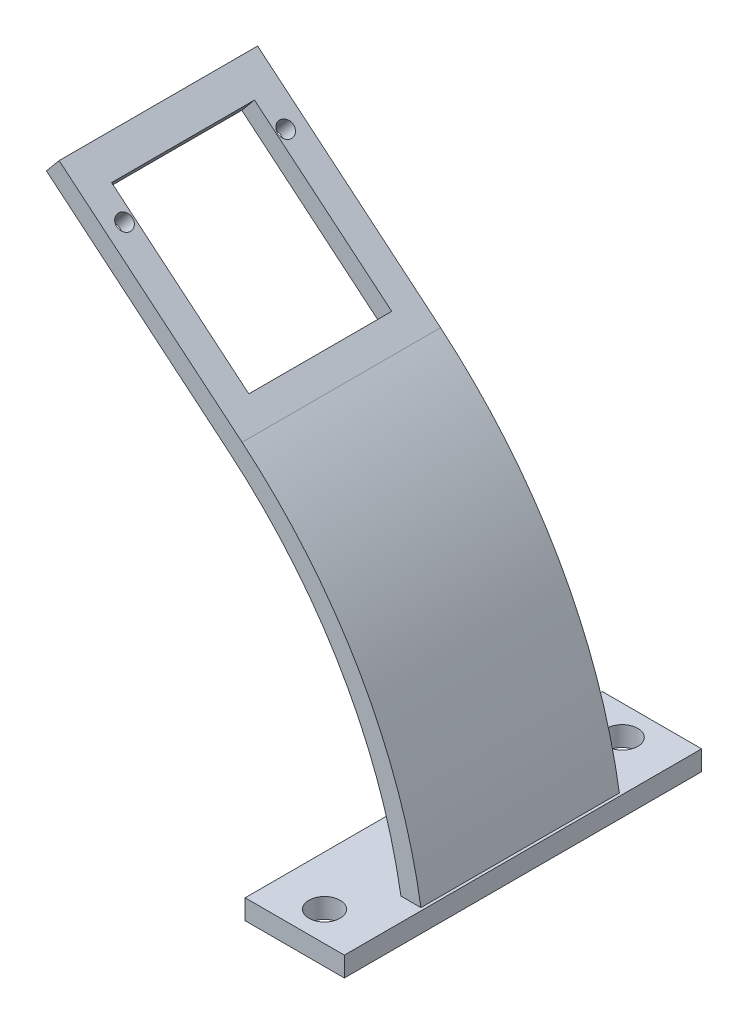
SolidWorks part; units mm, degrees
ref_plane "Front" through (0, 0, 0) normal (0, 0, 1) x (1, 0, 0)
ref_plane "Top" through (0, 0, 0) normal (0, 1, 0) x (1, 0, 0)
ref_plane "Right" through (0, 0, 0) normal (1, 0, 0) x (0, 0, -1)
sketch "Sketch1" plane through (0, 0, 0) normal (0, 0, 1) x (1, 0, 0)
  line L0 (-22.3321, 40.7208) -> (-45.7464, 60.2349)
  line L1 (-45.7464, 60.2349) -> (-44.1203, 62.1861)
  line L2 (-44.1203, 62.1861) -> (-20.706, 42.672)
  line L3 (0, 0) -> (2.54, 0)
  line L4 (55, 0) -> (-55, 0) construction
  arc A0 (0, 0) -> (-22.3321, 40.7208) centre (-62.9865, -8.059) ccw
  arc A1 (-20.706, 42.672) -> (2.54, 0) centre (-62.9399, -8.003) cw
  dimension "D3" = 63.5
  dimension "D4" = 39.809
  dimension "D1" = 2.54
  dimension "D2" = 2.54
  dimension "D5" = 30.48
  dimension "D6" = 30.48
  dimension "D7" = 42.672
extrude "Boss-Extrude1" add sketch "Sketch1" along normal blind 25.4
sketch "Sketch2" plane through (12.4995, 14.9977, 0) normal (0.6402, 0.7682, 0) x (0.7682, -0.6402, 0)
  line L0 (-73.7058, -25.4) -> (-73.7058, 0) construction
  line L1 (-69.591, -3.556) -> (-46.731, -3.556)
  line L2 (-69.591, -3.556) -> (-69.591, -21.844)
  line L3 (-69.591, -21.844) -> (-46.731, -21.844)
  line L4 (-46.731, -3.556) -> (-46.731, -21.844)
  line L5 (-71.0072, 0) -> (-73.7058, -25.4) construction
  line L6 (-55, 0) -> (55, 0) construction
  line L7 (-72.3565, -12.7) -> (-46.731, -12.7) construction
  line L8 (-43.2258, -25.4) -> (-73.7058, -25.4) construction
  circle A0 centre (-65.8846, -2.4168) radius 0.9995
  circle A1 centre (-65.8896, -23.034) radius 0.9995
  point P12 (-72.3565, -12.7)
  point P13 (-69.591, -12.7)
  dimension "D4" = 1.999
  dimension "D6" = 20.6172
  dimension "D1" = 22.86
  dimension "D2" = 18.288
  dimension "D3" = 4.1148
  dimension "D5" = 2.366
extrude "Cut-Extrude1" cut sketch "Sketch2" against normal up to next
sketch "Sketch3" plane through (0, 0, 0) normal (0, 1, 0) x (1, 0, 0)
  line L0 (-26.5575, 0) -> (26.5575, 0) construction
  line L1 (2.54, -35.56) -> (-10.16, -35.56)
  line L2 (2.54, -35.56) -> (2.54, 10.16)
  line L3 (2.54, 10.16) -> (-10.16, 10.16)
  line L4 (-10.16, -35.56) -> (-10.16, 10.16)
  line L5 (-20.706, -25.4) -> (2.54, -25.4) construction
  line L6 (2.54, -25.4) -> (2.54, 0) construction
  circle A0 centre (-3.81, 6.35) radius 2
  circle A1 centre (-3.81, -31.75) radius 2
  point P13 (-9.4613, -30.5716)
  point P14 (-10.9891, 6.35)
  point P17 (-13.97, 3.81)
  point P18 (-13.0544, -34.29)
  dimension "D1" = 4
  dimension "D2" = 4
  dimension "D5" = 6.35
  dimension "D3" = 38.1
  dimension "D4" = 6.35
  dimension "D6" = 10.16
  dimension "D7" = 10.16
  dimension "D8" = 12.7
extrude "Boss-Extrude2" add sketch "Sketch3" along normal blind 2.54
